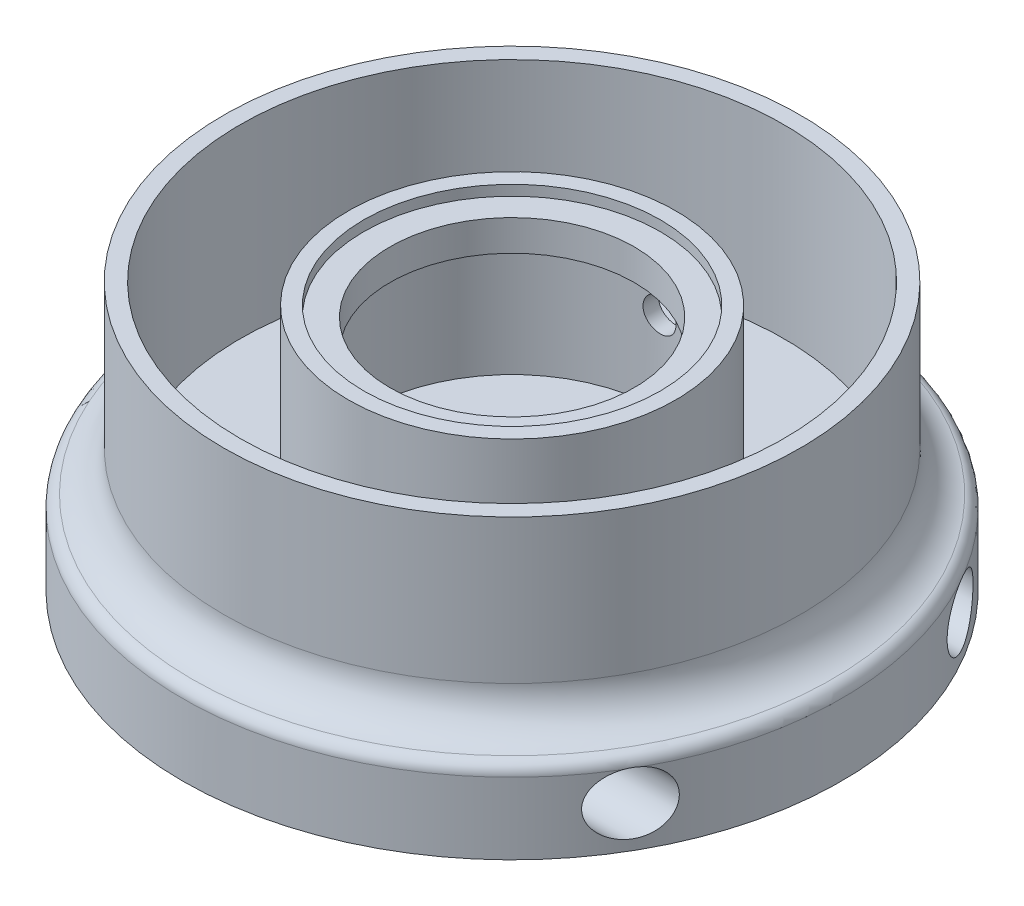
SolidWorks part; units mm, degrees
ref_plane "Front Plane" through (0, 0, 0) normal (0, 0, 1) x (1, 0, 0)
ref_plane "Top Plane" through (0, 0, 0) normal (0, 1, 0) x (1, 0, 0)
ref_plane "Right Plane" through (0, 0, 0) normal (1, 0, 0) x (0, 0, -1)
sketch "Sketch1" plane through (0, 0, 0) normal (0, 1, 0) x (1, 0, 0)
  circle A0 centre (0, 0) radius 101.6
  dimension "D1" = 203.2
extrude "Boss-Extrude1" add sketch "Sketch1" along normal blind 25.4
sketch "Sketch2" plane through (0, 0, 0) normal (1, 0, 0) x (0, 0, -1)
  line L0 (0, 0) -> (0, 19.5505) construction
  circle A1 centre (50.8, 12.7) radius 9.525
  circle A2 centre (-50.8, 12.7) radius 9.525
  dimension "D1" = 12.7
  dimension "D2" = 50.8
sketch "Sketch4" plane through (0, 25.4, 0) normal (0, 1, 0) x (1, 0, 0)
  circle A0 centre (0, 0) radius 88.9
  circle A1 centre (0, 0) radius 83.82
  dimension "D1" = 177.8
  dimension "D2" = 167.64
  dimension "D3" = 167.64
extrude "Boss-Extrude2" add sketch "Sketch4" along normal blind 57.15
extrude "Cut-Extrude4" cut sketch "Sketch2" against normal blind 101.6 and the other way blind 101.6
fillet "Fillet7" radius 12.7 1 edges at (0, 25.4, 88.9)
fillet "Fillet8" radius 3.81 1 edges at (0, 25.4, 101.6)
sketch "Sketch11" plane through (0, 25.4, 0) normal (0, 1, 0) x (1, 0, 0)
  circle A1 centre (0, 0) radius 50.4825
  circle A2 centre (0, 0) radius 45.72
  circle A3 centre (0, 0) radius 45.72
  dimension "D3" = 91.44
  dimension "D1" = 38.1
  dimension "D2" = 4.7625
extrude "Boss-Extrude5" add sketch "Sketch11" along normal blind 50.8
sketch "Sketch13" plane through (0, 0, 0) normal (0, 0, 1) x (1, 0, 0)
  line L0 (45.72, 63.5) -> (37.6512, 63.5)
  line L1 (45.72, 25.4) -> (45.72, 76.2) construction
  line L2 (37.6512, 63.5) -> (37.6512, 73.025)
  line L3 (37.6512, 73.025) -> (45.72, 73.025)
  line L4 (45.72, 73.025) -> (45.72, 63.5)
  dimension "D1" = 9.525
ref_axis "Axis2" through (0, 80.01, 0) along (0, -1, 0)
revolve "Revolve1" add sketch "Sketch13" angle 360 about axis through (0, 80.01, 0) along (0, -1, 0)
sketch "Sketch14" plane through (0, 0, 0) normal (0, 0, 1) x (1, 0, 0)
  circle A0 centre (0, 50.8) radius 5.08
  point P2 (0, 0)
extrude "Cut-Extrude5" cut sketch "Sketch14" against normal blind 50.8 contours A0
sketch "Sketch15" plane through (0, 0, 0) normal (0, -1, 0) x (1, 0, 0)
  circle A0 centre (0, 0) radius 3.175
extrude "Cut-Extrude6" cut sketch "Sketch15" against normal blind 101.6
sketch "Sketch16" plane through (0, 0, 0) normal (0, -1, 0) x (1, 0, 0)
  circle A0 centre (0, 0) radius 12.7
extrude "Cut-Extrude7" cut sketch "Sketch16" against normal blind 6.35
